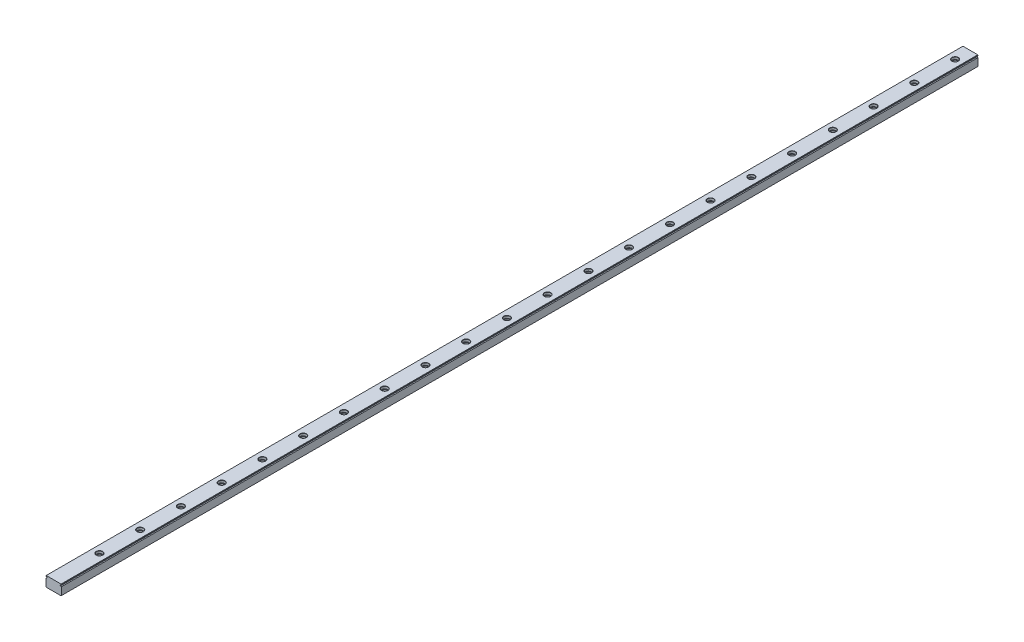
SolidWorks part; units mm, degrees
ref_plane "Спереди" through (0, 0, 0) normal (0, 0, 1) x (1, 0, 0)
ref_plane "Сверху" through (0, 0, 0) normal (0, 1, 0) x (1, 0, 0)
ref_plane "Справа" through (0, 0, 0) normal (1, 0, 0) x (0, 0, -1)
sketch "Sketch1" plane through (0, 0, 0) normal (0, 0, 1) x (1, 0, 0)
  line L0 (0, 0) -> (0, 4.3706) construction
  line L1 (-7.3, -5) -> (7.3, -5)
  line L2 (-7.5, -4.8) -> (-7.5, 2.7063)
  line L3 (-7.3, 5) -> (7.3, 5)
  line L4 (7.5, -4.8) -> (7.5, 2.7063)
  line L5 (-7.5, -5) -> (7.5, 5) construction
  line L6 (-7.5, 5) -> (7.5, -5) construction
  line L7 (-7.5, 4.2937) -> (-7.5, 4.8)
  line L8 (7.5, 4.2937) -> (7.5, 4.8)
  line L9 (-7.5, -4.8) -> (-7.3, -5)
  line L10 (7.3, -5) -> (7.5, -4.8)
  line L11 (7.3, 5) -> (7.5, 4.8)
  line L12 (-7.5, 4.8) -> (-7.3, 5)
  line L13 (6.8401, 3.25) -> (6.3401, 3.25)
  line L14 (-6.8401, 3.25) -> (-6.3401, 3.25)
  line L15 (6.3401, 3.25) -> (6.3401, 3.75)
  line L16 (-6.8401, 3.75) -> (-6.3401, 3.75)
  line L17 (-6.3401, 3.25) -> (-6.3401, 3.75)
  line L18 (6.8401, 3.75) -> (6.3401, 3.75)
  arc A0 (-7.5, 4.2937) -> (-6.8401, 3.75) centre (-7.6, 3.5) cw
  arc A1 (7.5, 4.2937) -> (6.8401, 3.75) centre (7.6, 3.5) ccw
  arc A2 (-6.8401, 3.25) -> (-7.5, 2.7063) centre (-7.6, 3.5) cw
  arc A3 (6.8401, 3.25) -> (7.5, 2.7063) centre (7.6, 3.5) ccw
  point P0 (0, 0)
  dimension "D4" = 0.8
  dimension "D5" = 0.1
  dimension "D1" = 15
  dimension "D2" = 10
  dimension "D3" = 1.5
  dimension "D6" = 0.5
  dimension "D7" = 0.5
extrude "Extrude1" add sketch "Sketch1" along normal blind 900
sketch "Sketch2" plane through (0, 5, 0) normal (0, 1, 0) x (1, 0, 0)
  line L0 (0, 0) -> (0, -15) construction
  circle A0 centre (0, -15) radius 2.25
  circle A1 centre (0, -15) radius 3
  dimension "D1" = 4.5
  dimension "D2" = 6
  dimension "D3" = 15
extrude "Extrude2" cut sketch "Sketch2" against normal up to next contours A0 region at (0, 5, 15)
extrude "Extrude4" cut sketch "Sketch" against normal blind 2.3
sketch "Sketch" plane through (0, 5, 0) normal (0, 1, 0) x (1, 0, 0) same geometry as "Sketch2"
chamfer "Chamfer1" distance 0.2 angle 45 2 edges at (0, -5, 17.25) (0, 5, 18)
pattern_linear "LPattern1" count 22 spacing 40 along (0, 0, 1) of "Extrude4", "Chamfer1", "Extrude2"
